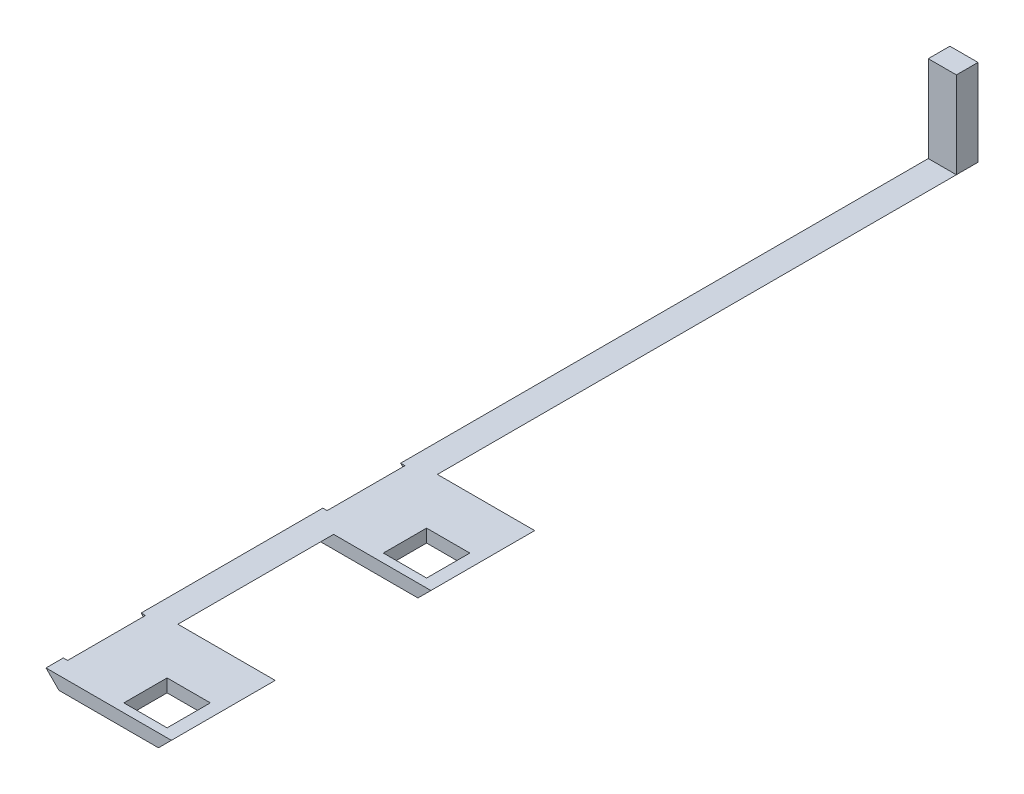
SolidWorks part; units mm, degrees
ref_plane "Płaszczyzna przednia" through (0, 0, 0) normal (0, 0, 1) x (1, 0, 0)
ref_plane "Płaszczyzna górna" through (0, 0, 0) normal (0, 1, 0) x (1, 0, 0)
ref_plane "Płaszczyzna prawa" through (0, 0, 0) normal (1, 0, 0) x (0, 0, -1)
sketch "Szkic6" plane through (0, 0, 0) normal (0, 1, 0) x (1, 0, 0)
  line L0 (0, 60) -> (22.5, 60)
  line L1 (0, 0) -> (22.5, 0)
  line L3 (0, 24) -> (22.5, 24)
  line L4 (22.5, 0) -> (22.5, 24)
  line L5 (11.25, 24) -> (11.25, 0) construction
  line L6 (0, 12) -> (22.5, 12) construction
  line L8 (0, 84) -> (22.5, 84)
  line L9 (22.5, 60) -> (22.5, 84)
  line L10 (11.25, 84) -> (11.25, 60) construction
  line L11 (0, 72) -> (22.5, 72) construction
  line L12 (0, 60) -> (0, 24)
  line L15 (0, 0) -> (-6.5, 0)
  line L16 (-6.5, 84) -> (-6.5, 0)
  line L17 (-3.25, 0) -> (-3.25, 60) construction
  line L18 (3.5, 42) -> (-6.5, 42) construction
  line L21 (-6.5, 84) -> (-6.5, 209)
  line L22 (-6.5, 209) -> (0, 209)
  line L23 (0, 84) -> (0, 209)
  line L24 (-3.25, 209) -> (-3.25, 60) construction
  line L25 (-6.5, 146.5) -> (0, 146.5) construction
  point P14 (11.25, 72)
  point P68 (11.25, 12)
  point P281 (-3.25, 42)
  point P384 (-3.25, 146.5)
  dimension "D1" = 24
  dimension "D2" = 6.5
  dimension "D4" = 60
  dimension "D5" = 22.5
  dimension "D6" = 125
  dimension "D3" = 2
extrude "Dodanie-wyciągnięcie4" add sketch "Szkic6" along normal blind 3
chamfer "Sfazowanie2" distance 3 angle 45 3 edges at (0, 0, -42) (22.5, 0, -72) (22.5, 0, -12)
sketch "Szkic7" plane through (0, 3, 0) normal (0, 1, 0) x (1, 0, 0)
  line L1 (-6.5, 209) -> (0, 209)
  line L2 (-6.5, 209) -> (-6.5, 204)
  line L3 (-6.5, 204) -> (0, 204)
  line L4 (0, 209) -> (0, 204)
  line L5 (-3.25, 204) -> (-3.25, 209) construction
  line L6 (-6.5, 206.5) -> (0, 206.5) construction
  line L7 (0, 209) -> (-6.5, 209) construction
  line L8 (0, 84) -> (0, 209) construction
  line L9 (-6.5, 209) -> (-6.5, 0) construction
  point P132 (-3.25, 206.5)
  dimension "D1" = 5
extrude "Dodanie-wyciągnięcie5" add sketch "Szkic7" along normal blind 20
fillet "Sfazowanie3" radius 3 2 edges at (-6.5, 0, -104.5) (0, 0, -146.5) profile chamfer
chamfer "Chamfer1" [suppressed] distance 2 angle 45
sketch "Szkic8" plane through (0, 3, 0) normal (0, 1, 0) x (1, 0, 0)
  line L0 (19.5, 12) -> (19.5, 2)
  line L1 (9.5, 12) -> (9.5, 2)
  line L2 (9.5, 62) -> (19.5, 62)
  line L3 (19.5, 72) -> (9.5, 72)
  line L4 (19.5, 72) -> (19.5, 62)
  line L5 (9.5, 72) -> (9.5, 62)
  line L6 (9.5, 2) -> (19.5, 2)
  line L7 (19.5, 12) -> (9.5, 12)
extrude "Wytnij-wyciągnięcie1" cut sketch "Szkic8" against normal blind 10
sketch "Szkic9" plane through (0, 3, 0) normal (0, 1, 0) x (1, 0, 0)
  line L0 (-8, 67) -> (-8, 7) construction
  line L1 (-6.5, 0) -> (22.5, 0) construction
  line L2 (-8, 67) -> (-8, 69) construction
  line L3 (-5.5, 82) -> (-10.5, 82)
  line L4 (-5.5, 82) -> (-5.5, 64)
  line L5 (-5.5, 64) -> (-10.5, 64)
  line L6 (-10.5, 82) -> (-10.5, 64)
  line L7 (-5.5, 82) -> (-10.5, 64) construction
  line L8 (-5.5, 64) -> (-10.5, 82) construction
  line L9 (-8, 67) -> (-8, 65) construction
  line L10 (-8, 7) -> (-8, 5) construction
  line L11 (-5.5, 22) -> (-10.5, 22)
  line L12 (-5.5, 22) -> (-5.5, 4)
  line L13 (-5.5, 4) -> (-10.5, 4)
  line L14 (-10.5, 22) -> (-10.5, 4)
  line L15 (-5.5, 22) -> (-10.5, 4) construction
  line L16 (-5.5, 4) -> (-10.5, 22) construction
  line L17 (-8, 7) -> (-8, 9) construction
  circle A2 centre (-8, 7) radius 2 construction
  circle A3 centre (-8, 67) radius 2 construction
  point P7 (-8, 73)
  point P12 (-8, 13)
  dimension "D5" = 4
  dimension "D1" = 60
  dimension "D2" = 7
  dimension "D3" = 8
  dimension "D4" = 1
  dimension "D6" = 5
  dimension "D7" = 13
  dimension "D8" = 5
  dimension "D9" = 1
  dimension "D10" = 13
extrude "Wytnij-wyciągnięcie2" cut sketch "Szkic9" against normal blind 10
